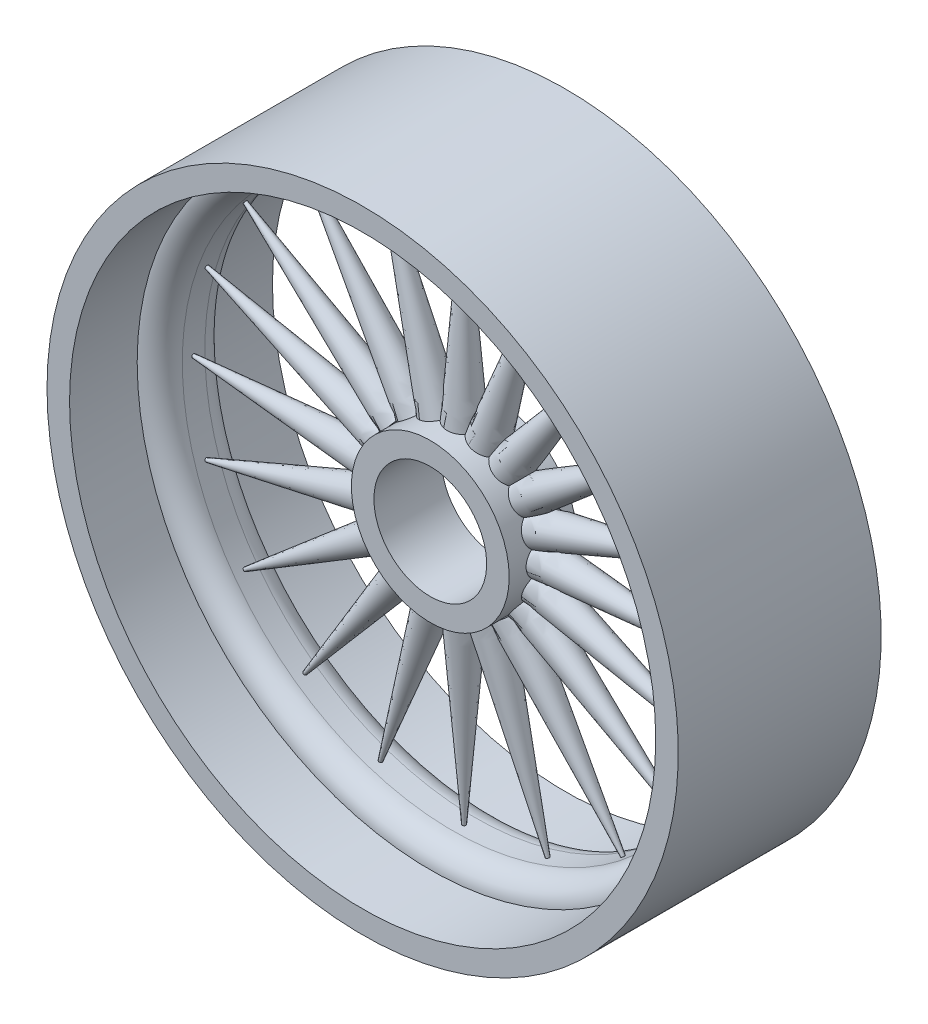
SolidWorks part; units mm, degrees
ref_plane "Front Plane" through (0, 0, 0) normal (0, 0, 1) x (1, 0, 0)
ref_plane "Top Plane" through (0, 0, 0) normal (0, 1, 0) x (1, 0, 0)
ref_plane "Right Plane" through (0, 0, 0) normal (1, 0, 0) x (0, 0, -1)
sketch "Sketch2" plane through (0, 0, 0) normal (0, 0, 1) x (1, 0, 0)
  circle A0 centre (0, 0) radius 6.35
  circle A1 centre (0, 0) radius 35.56
  dimension "D1" = 12.7
  dimension "D2" = 71.12
extrude "Boss-Extrude1" add sketch "Sketch2" along normal mid plane 7.62
sketch "Sketch5" plane through (0, 0, 3.81) normal (0, 0, 1) x (1, 0, 0)
  line L0 (0, 0) -> (0, 35.56) construction
  line L1 (0, 0) -> (0, -35.56) construction
  circle A0 centre (0, 0) radius 35.56 construction
  dimension "D1" = 35.56
sketch "Sketch6" plane through (0, 0, -3.81) normal (0, 0, -1) x (-1, 0, 0)
  line L0 (0, 35.56) -> (0, -35.56) construction
ref_plane "Plane1" through (0, 35.56, 3.81) normal (0, 1, 0) x (1, 0, 0)
ref_axis "Axis2" through (0, 0, 3.81) along (0, 0, -1)
sketch "Sketch11" plane through (0, 0, 3.81) normal (0, 0, 1) x (1, 0, 0)
  circle A0 centre (0, 0) radius 30.48
  circle A1 centre (0, 0) radius 6.35
  circle A2 centre (0, 0) radius 8.89
  circle A3 centre (0, 0) radius 35.56 construction
  dimension "D1" = 2.54
  dimension "D2" = 5.08
extrude "Cut-Extrude2" cut sketch "Sketch11" against normal through all and the other way through all contours A0 A2 region at (-29.6179, 0, 3.81)
sketch "Sketch12" plane through (0, 0, -3.81) normal (0, 0, -1) x (-1, 0, 0)
  line L0 (0, 8.89) -> (0, -8.89) construction
  line L1 (0, 8.89) -> (0, -8.89) construction
  line L2 (-8.89, 0) -> (8.89, 0) construction
  line L3 (0, -8.89) -> (0, 0) construction
  line L4 (0, 0) -> (-8.89, 0) construction
  line L5 (-8.89, 0) -> (8.89, 0) construction
  circle A0 centre (0, 0) radius 8.89 construction
sketch "Sketch13" plane through (0, 0, 3.81) normal (0, 0, 1) x (1, 0, 0)
  line L0 (0, 8.89) -> (0, -8.89) construction
  line L1 (0, -8.89) -> (0, 0) construction
  line L2 (0, 0) -> (-8.89, 0) construction
  line L3 (-8.89, 0) -> (8.89, 0) construction
ref_plane "Plane3" through (-8.89, 0, 3.81) normal (-1, 0, 0) x (0, 0, 1)
sketch "Sketch14" plane through (-8.89, 0, 3.81) normal (-1, 0, 0) x (0, 0, 1)
  line L0 (-7.62, 0) -> (0, 0) construction
  line L1 (0, -8.89) -> (0, 0) construction
  point P9 (-3.81, 0)
fillet "Fillet1" radius 2.54 2 edges at (30.48, 0, 3.81) (30.48, 0, -3.81)
ref_plane "Plane6" through (0, 0, -3.81) normal (0, 0, -1) x (-1, 0, 0)
ref_plane "Plane7" through (0, 0, 3.81) normal (0, 0, 1) x (1, 0, 0)
sketch "Sketch16" plane through (0, 0, 3.81) normal (0, 0, 1) x (1, 0, 0)
  circle A0 centre (0, 0) radius 33.02
  circle A1 centre (0, 0) radius 35.56
  dimension "D1" = 66.04
  dimension "D2" = 71.12
sketch "Sketch19" plane through (0, 0, 3.81) normal (0, 0, 1) x (1, 0, 0)
  circle A0 centre (0, 0) radius 33.02
  circle A1 centre (0, 0) radius 35.56
extrude "Boss-Extrude3" add sketch "Sketch19" along normal blind 7.62 and the other way blind 15.24 contours A1 | A0
ref_plane "Plane8" through (-8.89, 0, 0) normal (-1, 0, 0) x (0, 0, 1)
ref_plane "Plane9" through (0, 0, 0) normal (0, 1, 0) x (1, 0, 0)
sketch "Sketch20" plane through (0, 0, 0) normal (0, 1, 0) x (1, 0, 0)
  line L0 (-8.89, -3.81) -> (-8.89, -11.43) construction
  line L1 (-8.89, -11.43) -> (-33.02, -11.43) construction
  line L2 (-33.02, -11.43) -> (-33.02, -3.81) construction
  line L3 (-33.02, -11.43) -> (33.02, -11.43) construction
  line L4 (-33.02, -3.81) -> (-33.02, 3.81) construction
  line L5 (-8.89, -1.905) -> (-8.89, 0)
  line L6 (-8.89, -3.81) -> (-8.89, 0) construction
  line L7 (-8.89, 3.81) -> (-8.89, -3.81) construction
  line L8 (-8.89, 0) -> (-33.02, 0) construction
  line L9 (-8.89, -1.905) -> (-33.02, -1.905) construction
  line L10 (-33.02, -1.905) -> (-33.02, 0) construction
  line L11 (-8.89, 0) -> (-33.02, 0)
  line L12 (-33.02, -1.905) -> (-8.89, 0) construction
  line L13 (-33.02, 0) -> (-8.89, -1.905)
  dimension "D1" = 7.62
  dimension "D2" = 7.62
  dimension "D3" = 7.62
  dimension "D4" = 3.81
revolve "Revolve1" add sketch "Sketch20" angle 360 about L11
pattern_circular "CirPattern1" count 20 every 18 about axis through (0, 0, 3.81) along (0, 0, -1) of "Revolve1"
